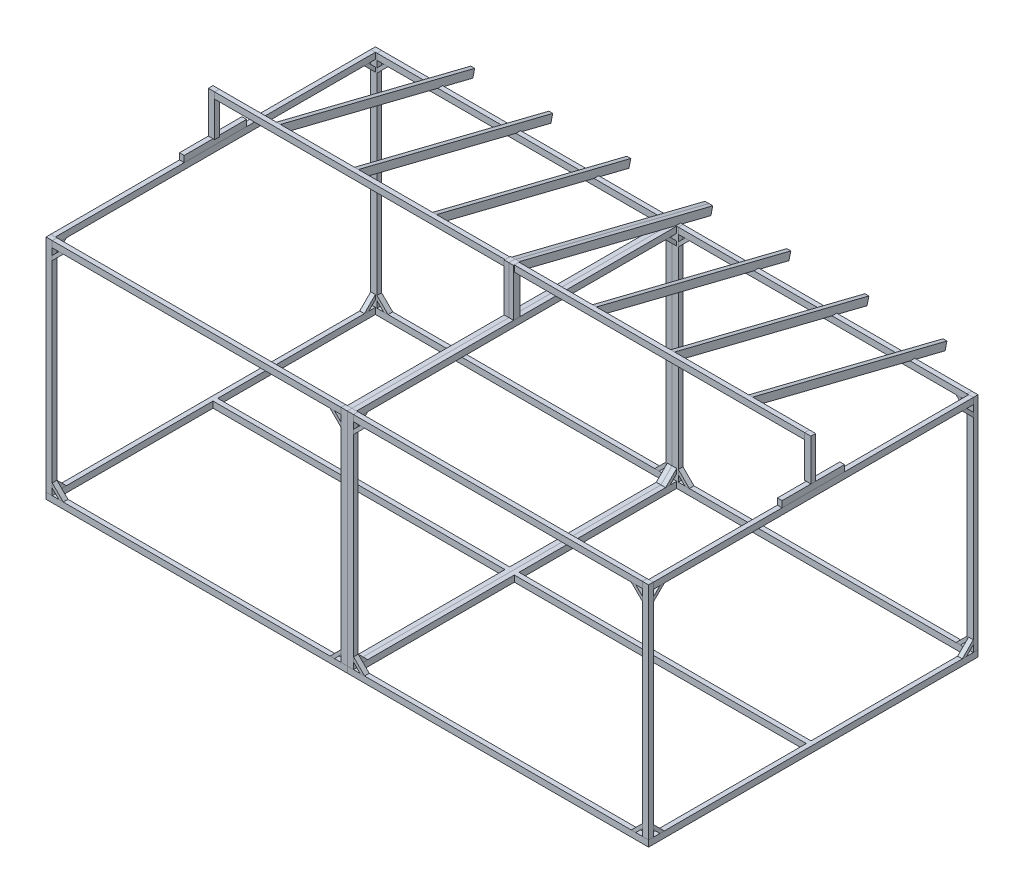
SolidWorks part; units mm, degrees
other "DetailItem8"
other "DetailItem9"
other "DetailItem10"
other "DetailItem12"
other "DetailItem13"
other "DetailItem14"
other "DetailItem15"
other "DetailItem16"
other "DetailItem17"
other "DetailItem18"
other "DetailItem19"
other "DetailItem21"
ref_plane "Front Plane" through (0, 0, 0) normal (0, 0, 1) x (1, 0, 0)
ref_plane "Top Plane" through (0, 0, 0) normal (0, 1, 0) x (1, 0, 0)
ref_plane "Right Plane" through (0, 0, 0) normal (1, 0, 0) x (0, 0, -1)
other "Configuration Table"
sketch "MetalBase" plane through (0, 0, 0) normal (0, 1, 0) x (1, 0, 0)
  line L0 (-60, -60) -> (7660, -60)
  line L1 (0, 0) -> (7600, 0)
  line L2 (0, 0) -> (0, 2020)
  line L3 (0, 4100) -> (7600, 4100)
  line L4 (7600, 0) -> (7600, 2020)
  line L5 (7660, -60) -> (7660, 4160)
  line L6 (-60, 4160) -> (7660, 4160)
  line L7 (-60, -60) -> (-60, 4160)
  line L8 (0, 2050) -> (7600, 2050) construction
  line L9 (0, 2020) -> (7600, 2020)
  line L10 (0, 2080) -> (7600, 2080)
  line L11 (0, 2080) -> (0, 4100)
  line L12 (7600, 2080) -> (7600, 4100)
  line L13 (0, 0) -> (0, 4100) construction
  line L15 (7600, 0) -> (7600, 4100) construction
  point P15 (7660, 2050)
  dimension "D1" = 4100
  dimension "D2" = 7600
  dimension "D6" = 4220
  dimension "D7" = 7720
  dimension "D3" = 60
  dimension "D4" = 30
  dimension "D5" = 30
sketch "InternalSpace" plane through (0, 0, 0) normal (0, 1, 0) x (1, 0, 0)
  line L26 (50, 50) -> (7550, 50)
  line L27 (7550, 50) -> (7550, 4050)
  line L28 (7550, 4050) -> (50, 4050)
  line L29 (50, 4050) -> (50, 50)
  line L30 (50, 50) -> (7550, 50)
  line L31 (7550, 50) -> (7550, 4050)
  line L32 (7550, 4050) -> (50, 4050)
  line L33 (50, 4050) -> (50, 50)
  dimension "D2" = 4000
  dimension "D3" = 7500
  dimension "D1" = 110
sketch "Furniture" [suppressed] plane through (0, 0, 0) normal (0, 1, 0) x (1, 0, 0)
  line L0 (6750, 2050) -> (6750, 4050)
  line L1 (2200, 2550) -> (1400, 2550)
  line L2 (2200, 2550) -> (2200, 4050)
  line L3 (2200, 4050) -> (1400, 4050)
  line L4 (1400, 2550) -> (1400, 4050)
  line L5 (1050, 50) -> (50, 50)
  line L6 (1050, 50) -> (1050, 2050)
  line L7 (1050, 2050) -> (50, 2050)
  line L8 (50, 50) -> (50, 2050)
  line L9 (6350, 2110) -> (7550, 2110)
  line L10 (2200, 4050) -> (2200, 150)
  line L11 (0, 0) -> (7600, 0) construction
  line L12 (6350, 50) -> (6350, 2110)
  line L13 (6470, 50) -> (6470, 1990)
  line L15 (2200, 2050) -> (7550, 2050) construction
  line L17 (1979.5569, 919.0285) -> (2200, 150)
  line L18 (6350, 150) -> (5722.0427, 459.305)
  line L19 (6710, 1120.0467) -> (7310, 1120.0467)
  line L24 (6710, 1120.0467) -> (6710, 1880.0467)
  line L25 (6710, 1880.0467) -> (7310, 1880.0467)
  line L26 (7310, 1120.0467) -> (7310, 1880.0467)
  line L27 (6350, 2110) -> (5750, 2110)
  line L28 (6350, 2110) -> (6350, 1510)
  line L29 (6350, 1510) -> (5750, 1510)
  line L30 (5750, 2110) -> (5750, 1510)
  line L31 (2320, 2050) -> (4320, 2050) construction
  line L32 (4320, 2050) -> (4320, 4050) construction
  line L33 (2200, 150) -> (2499.3532, 150) construction
  line L34 (2499.3532, 150) -> (2499.3532, 981.1813) construction
  line L35 (2499.3532, 981.1813) -> (2200, 981.1813) construction
  line L36 (2320, 4050) -> (2320, 150)
  line L37 (2200, 150) -> (2200, 50)
  line L38 (50, 50) -> (7550, 50) construction
  line L39 (2320, 150) -> (2320, 50)
  line L40 (7550, 4050) -> (50, 4050) construction
  line L41 (7550, 50) -> (7550, 4050) construction
  line L42 (50, 4050) -> (50, 50) construction
  line L43 (7550, 4050) -> (50, 4050) construction
  line L44 (7550, 50) -> (7550, 4050) construction
  line L45 (50, 50) -> (7550, 50) construction
  line L46 (50, 4050) -> (50, 50) construction
  line L47 (7010, 1120.0467) -> (7010, 1445.9123) construction
  line L48 (6470, 1990) -> (7550, 1990)
  line L49 (-60, -60) -> (-60, 4160) construction
  line L50 (7550, 809.8905) -> (7383.7397, 809.8905)
  line L51 (7550, 809.8905) -> (7550, 230.8186)
  line L52 (7550, 230.8186) -> (7383.7397, 230.8186)
  line L53 (7283.7397, 709.8905) -> (7283.7397, 330.8186)
  line L54 (7660, 4160) -> (-60, 4160) construction
  line L55 (-60, 4160) -> (-60, -60) construction
  line L56 (-60, -60) -> (7660, -60) construction
  line L57 (7660, -60) -> (7660, 4160) construction
  arc A1 (1979.5569, 919.0285) -> (1414.1883, 0) centre (2200, 150) ccw construction
  arc A2 (5722.0427, 459.305) -> (6350, 850) centre (6350, 150) cw construction
  arc A3 (7383.7397, 230.8186) -> (7283.7397, 330.8186) centre (7383.7397, 330.8186) cw
  arc A4 (7383.7397, 809.8905) -> (7283.7397, 709.8905) centre (7383.7397, 709.8905) ccw
  point P56 (7010, 1990)
  dimension "D13" = 600
  dimension "D21" = 100
  dimension "D1" = 1500
  dimension "D2" = 800
  dimension "D3" = 2000
  dimension "D4" = 1000
  dimension "D5" = 100
  dimension "D6" = 60
  dimension "D7" = 700
  dimension "D8" = 600
  dimension "D9" = 2260
  dimension "D10" = 800
  dimension "D11" = 100
  dimension "D12" = 760
  dimension "D14" = 2000
  dimension "D15" = 800
  dimension "D16" = 2000
  dimension "D17" = 600
  dimension "D18" = 60
  dimension "D19" = 4150
  dimension "D20" = 120
  dimension "D22" = 120
  dimension "D23" = 110
  dimension "D25" = 4220
  dimension "D26" = 1200
  dimension "D27" = 4030
  dimension "D24" = 110
sketch "Metal frame" plane through (0, 0, 0) normal (0, 1, 0) x (1, 0, 0)
  line L0 (0, 4100) -> (7600, 4100) construction
  line L1 (0, 4100) -> (7600, 4100)
  line L3 (0, 0) -> (0, 2020)
  line L4 (0, 0) -> (7600, 0) construction
  line L5 (0, 0) -> (7600, 0)
  line L7 (7600, 0) -> (7600, 2020)
  line L8 (-60, 4160) -> (7660, 4160)
  line L9 (7660, -60) -> (7660, 4160)
  line L10 (-60, -60) -> (7660, -60)
  line L11 (-60, -60) -> (-60, 4160)
  line L12 (0, 2050) -> (62.1159, 2050) construction
  line L13 (7600, 2080) -> (0, 2080)
  line L15 (7600, 2020) -> (0, 2020)
  line L17 (7600, 2080) -> (7600, 4100)
  line L18 (0, 2080) -> (0, 4100)
  line L19 (7600, 0) -> (7600, 4100) construction
  line L21 (0, 0) -> (0, 4100) construction
  point P14 (-60, 2050)
  dimension "D2" = 7720
  dimension "D3" = 4220
  dimension "D4" = 60
  dimension "D1" = 60
sketch "Walls bottom" plane through (0, 0, 0) normal (0, 1, 0) x (1, 0, 0)
  line L0 (-60, 4160) -> (7660, 4160) construction
  line L2 (-60, -60) -> (7660, -60) construction
  line L3 (7660, -60) -> (7660, 4160) construction
  line L4 (-60, -60) -> (-60, 4160) construction
  line L5 (-60, -60) -> (7660, -60)
  line L6 (7660, -60) -> (7660, 4160)
  line L7 (-60, 4160) -> (7660, 4160)
  line L8 (-60, -60) -> (-60, 4160)
  line L9 (40, 40) -> (40, 4060)
  line L10 (40, 4060) -> (7560, 4060)
  line L11 (7560, 40) -> (7560, 4060)
  line L12 (40, 40) -> (7560, 40)
  dimension "D2" = 4020
  dimension "D3" = 7520
  dimension "D4" = 7720
  dimension "D5" = 4220
  dimension "D1" = 100
sketch "Sketch15" [suppressed] plane through (0, 0, 0) normal (0, 1, 0) x (1, 0, 0)
  line L2 (7550, 50) -> (5502.4266, 50)
  line L3 (7550, 50) -> (7550, 1250)
  line L4 (7550, 1250) -> (5502.4266, 1250)
  line L5 (5502.4266, 50) -> (5502.4266, 1250)
  dimension "D1" = 1200
extrude "MetalFrame" add sketch "Metal frame" against normal blind 80 contours L11 L10 L9 L8 L15 L7 L5 L3 L13 L18 L1 L17 region at (3800, 0, -2050)
sketch "Sketch18" plane through (0, 0, 0) normal (0, 1, 0) x (1, 0, 0)
  line L0 (0, 0) -> (7600, 0) construction
  line L1 (3800, -1014.8769) -> (8467.9433, -1014.8769)
  line L2 (3800, -1014.8769) -> (3800, 5493.3133)
  line L3 (3800, 5493.3133) -> (8467.9433, 5493.3133)
  line L4 (8467.9433, -1014.8769) -> (8467.9433, 5493.3133)
  point P6 (3800, 0)
extrude "Cut-Extrude1" cut sketch "Sketch18" against normal through all
sketch "Sketch19" plane through (0, 0, 0) normal (0, 1, 0) x (1, 0, 0)
  line L0 (0, 0) -> (3800, 0) construction
  line L1 (3800, 4100) -> (3740, 4100)
  line L2 (3800, 4100) -> (3800, 0)
  line L3 (3800, 0) -> (3740, 0)
  line L4 (3740, 4100) -> (3740, 0)
  dimension "D1" = 60
extrude "Boss-Extrude1" add sketch "Sketch19" against normal blind 80
sketch "Roof" plane through (0, 0, 0) normal (1, 0, 0) x (0, 0, -1)
  line L0 (2050, 0) -> (2050, 3357.5) construction
  line L1 (4160, 0) -> (-60, 0) construction
  line L2 (4160, 0) -> (4160, 2830) construction
  line L3 (4160, 2830) -> (2050, 3357.5) construction
  line L4 (2050, 3357.5) -> (5424.8088, 3357.5) construction
  line L5 (4160, 2830) -> (4548.057, 2732.9857) construction
  line L6 (4160, 150) -> (-211.81, 150) construction
  line L7 (4160, 2830) -> (2960, 2830)
  line L8 (2960, 2830) -> (2960, 3130)
  line L9 (4160, 2750) -> (2401.0379, 2750) construction
  dimension "D2" = 1200
  dimension "D3" = 150
  dimension "D4" = 2174.9382
  dimension "D5" = 400
  dimension "D6" = 2574.9382
  dimension "D7" = 2830
  dimension "D8" = 300
  dimension "D9" = 3207.5
  dimension "D10" = 14.036
  dimension "D11" = 80
  dimension "D12" = 2600
sketch "Sketch23" plane through (-60, 0, 0) normal (1, 0, 0) x (0, 0, -1)
  line L0 (2050, 0) -> (2050, 3357.5) construction
  line L1 (4160, 0) -> (4100, 0)
  line L2 (4160, 0) -> (4160, 2830)
  line L3 (4160, 2830) -> (4100, 2830)
  line L4 (4100, 0) -> (4100, 2830)
  line L5 (0, 0) -> (0, 2830)
  line L6 (-60, 2830) -> (0, 2830)
  line L7 (-60, 0) -> (-60, 2830)
  line L8 (-60, 0) -> (0, 0)
  line L10 (0, 2830) -> (4100, 2830)
  line L11 (0, 2830) -> (0, 2750)
  line L12 (0, 2750) -> (4100, 2750)
  line L13 (4100, 2830) -> (4100, 2750)
  line M8 (-60, 0) -> (4160, 0)
  dimension "D1" = 60
  dimension "D2" = 80
extrude "Boss-Extrude5" add sketch "Sketch23" along normal blind 80 separate body contours L4 L3 L2 M8 | L7 L6 L5 M8 region at (-60, 1415, -4130) region at (-60, 1415, 30)
extrude "Boss-Extrude6" add sketch "Sketch23<3>" along normal blind 60 separate body contours L0 L12 L5 L10 | L12 L0 L10 L4 region at (-60, 2790, -1025) region at (-60, 2790, -3075)
sketch "Sketch23<3>" plane through (-60, 0, 0) normal (1, 0, 0) x (0, 0, -1) same geometry as "Sketch23"
extrude "Boss-Extrude7" add sketch "Sketch23<5>" against normal blind 80 from surface separate body contours L4 L3 L2 M8 | L7 L6 L5 M8 region at (-60, 1415, -4130) region at (-60, 1415, 30) starting at face at (3800, -40, -2050)
sketch "Sketch23<5>" plane through (-60, 0, 0) normal (1, 0, 0) x (0, 0, -1) same geometry as "Sketch23"
extrude "Boss-Extrude8" add sketch "Sketch23<6>" against normal blind 60 from surface separate body contours L12 L0 L10 L4 | L0 L12 L5 L10 region at (-60, 2790, -1025) region at (-60, 2790, -3075) starting at face at (3800, 1415, 30)
sketch "Sketch23<6>" plane through (-60, 0, 0) normal (1, 0, 0) x (0, 0, -1) same geometry as "Sketch23"
sketch "Sketch24" plane through (0, 2830, 0) normal (0, 1, 0) x (1, 0, 0)
  line L1 (20, 4160) -> (3720, 4160)
  line L2 (20, 4160) -> (20, 4100)
  line L3 (20, 4100) -> (3720, 4100)
  line L4 (3720, 4160) -> (3720, 4100)
  line L5 (20, 0) -> (3720, 0)
  line L6 (20, 0) -> (20, -60)
  line L7 (20, -60) -> (3720, -60)
  line L8 (3720, 0) -> (3720, -60)
extrude "Boss-Extrude9" add sketch "Sketch24" against normal blind 80 separate body
sketch "Sketch25" plane through (3800, 0, 0) normal (1, 0, 0) x (0, 0, -1)
  line L5 (2020, 2910) -> (2080, 2910)
  line L6 (2020, 2910) -> (2020, 3440)
  line L7 (2020, 3440) -> (2080, 3440)
  line L8 (2080, 2910) -> (2080, 3440)
  line L9 (2050, 0) -> (2050, 3357.5) construction
  line L10 (0, 2830) -> (4100, 2830) construction
  line L12 (1650, 2830) -> (2450, 2830)
  line L13 (1650, 2830) -> (1650, 2910)
  line L14 (1650, 2910) -> (2450, 2910)
  line L15 (2450, 2830) -> (2450, 2910)
  point P7 (2050, 3440)
  point P11 (2050, 2910)
  line M8 (4100, 2830) -> (0, 2830)
  dimension "D1" = 530
  dimension "D2" = 60
  dimension "D4" = 800
  dimension "D5" = 80
extrude "Boss-Extrude10" add sketch "Sketch25" along normal blind 80 from surface separate body contours L5 L8 L7 L6 region at (3800, 3175, -2050) starting at face at (-60, 2790, -2050)
extrude "Boss-Extrude13" add sketch "Sketch25<4>" against normal blind 60 from surface separate body contours L15 L14 L5 L13 M8 region at (3800, 2870, -2050) starting at face at (0, 2790, -2050)
sketch "Sketch25<4>" plane through (3800, 0, 0) normal (1, 0, 0) x (0, 0, -1) same geometry as "Sketch25"
extrude "Boss-Extrude20" add sketch "Sketch25<5>" against normal blind 60 separate body contours L15 L14 L5 L13 M8 region at (3800, 2870, -2050)
sketch "Sketch25<5>" plane through (3800, 0, 0) normal (1, 0, 0) x (0, 0, -1) same geometry as "Sketch25"
sketch "Sketch33" plane through (0, 2910, 0) normal (0, 1, 0) x (1, 0, 0)
  line L0 (3740, 1650) -> (3740, 2450) construction
  line L1 (3740, 2090) -> (3800, 2090)
  line L2 (3740, 2090) -> (3740, 2010)
  line L3 (3740, 2010) -> (3800, 2010)
  line L4 (3800, 2090) -> (3800, 2010)
  line L5 (3800, 1650) -> (3800, 2450) construction
  point P8 (3740, 2050)
  point P9 (3740, 2050)
  dimension "D1" = 80
extrude "Boss-Extrude21" add sketch "Sketch33" along normal up to surface (530 mm away) separate body up to face at (-20, 3440, -2050)
sketch "Sketch26" plane through (3800, 0, 0) normal (1, 0, 0) x (0, 0, -1)
  line L0 (4548.057, 2717.9857) -> (4160, 2815)
  line L1 (4548.057, 2717.9857) -> (4572.3106, 2815)
  line L3 (4572.3106, 2815) -> (2080, 3438.0776)
  line L4 (4100, 2815) -> (4100, 2830) construction
  line L5 (4100, 2830) -> (4160, 2830)
  line L6 (4160, 2830) -> (4160, 2815)
  line L7 (2080, 3335) -> (2080, 3438.0776)
  line L8 (4100, 2830) -> (2080, 3335)
  dimension "D1" = 100
extrude "Boss-Extrude12" add sketch "Sketch26" against normal blind 50 separate body
pattern_linear "LPattern1" count 4 spacing 1000 along (-1, 0, 0) of bodies 346
ref_plane "Plane1" through (1870, 0, 0) normal (-1, 0, 0) x (0, 0, 1)
sketch "Sketch27" plane through (3740, 0, 0) normal (-1, 0, 0) x (0, 0, 1)
  line L0 (-2020, 2910) -> (-2020, 3440) construction
  line L1 (-2080, 3440) -> (-2020, 3440)
  line L2 (-2080, 3440) -> (-2080, 3360)
  line L3 (-2080, 3360) -> (-2020, 3360)
  line L4 (-2020, 3440) -> (-2020, 3360)
  line L5 (-2050, 0) -> (-2050, 3357.5) construction
  point P4 (-2050, 3440)
  dimension "D1" = 80
  dimension "D2" = 60
extrude "Boss-Extrude22" add sketch "Sketch27" along normal up to surface (3720 mm away) separate body up to face at (20, 3175, -2050)
mirror "Mirror2" about plane through (3800, -80, 1014.8769) normal (-1, 0, 0) of bodies 336 338 340 342 335 337 339 341 330 412 411 349 348 347 346 410 350 351 354 352 353
sketch "Sketch28" plane through (0, 0, 60) normal (0, 0, 1) x (1, 0, 0)
  line L0 (20, 2665.1472) -> (104.8528, 2750)
  line L1 (20, 2750) -> (3720, 2750) construction
  line L2 (20, 0) -> (20, 2830) construction
  line L3 (20, 2608.5786) -> (161.4214, 2750)
  line L4 (20, 2665.1472) -> (20, 2750) construction
  line L5 (20, 2750) -> (104.8528, 2750) construction
  line L6 (3720, 2750) -> (20, 0) construction
  line L7 (20, 2750) -> (3720, 0) construction
  line L8 (104.8528, 2750) -> (161.4214, 2750)
  line L9 (20, 2665.1472) -> (20, 2608.5786)
  line L10 (1870, 1375) -> (1870, 2476.0047) construction
  line L11 (1870, 1375) -> (689.8346, 1375) construction
  line L12 (20, 0) -> (104.8528, 0) construction
  line L13 (20, 84.8528) -> (20, 0) construction
  line L14 (20, 84.8528) -> (20, 141.4214)
  line L15 (104.8528, 0) -> (161.4214, 0)
  line L16 (20, 141.4214) -> (161.4214, 0)
  line L17 (20, 84.8528) -> (104.8528, 0)
  line L18 (3720, 84.8528) -> (3720, 0) construction
  line L19 (3720, 0) -> (3635.1472, 0) construction
  line L20 (3720, 2750) -> (3635.1472, 2750) construction
  line L21 (3720, 2665.1472) -> (3720, 2750) construction
  line L22 (3720, 84.8528) -> (3635.1472, 0)
  line L23 (3720, 141.4214) -> (3578.5786, 0)
  line L24 (3635.1472, 0) -> (3578.5786, 0)
  line L25 (3720, 84.8528) -> (3720, 141.4214)
  line L26 (3720, 2665.1472) -> (3720, 2608.5786)
  line L27 (3635.1472, 2750) -> (3578.5786, 2750)
  line L28 (3720, 2608.5786) -> (3578.5786, 2750)
  line L29 (3720, 2665.1472) -> (3635.1472, 2750)
  line L30 (3800, -80) -> (3800, -237.922) construction
  line L31 (3880, 2665.1472) -> (3880, 2750) construction
  line L32 (3880, 2750) -> (3964.8528, 2750) construction
  line L33 (3880, 0) -> (3964.8528, 0) construction
  line L34 (3880, 84.8528) -> (3880, 0) construction
  line L35 (7580, 84.8528) -> (7580, 0) construction
  line L36 (7580, 0) -> (7495.1472, 0) construction
  line L37 (5730, 1375) -> (6910.1654, 1375) construction
  line L38 (5730, 1375) -> (5730, 2476.0047) construction
  line L39 (7580, 2750) -> (3880, 0) construction
  line L40 (3880, 2750) -> (7580, 0) construction
  line L41 (7580, 2750) -> (7495.1472, 2750) construction
  line L42 (7580, 2665.1472) -> (7580, 2750) construction
  line L43 (3880, 2665.1472) -> (3964.8528, 2750)
  line L44 (3880, 2608.5786) -> (4021.4214, 2750)
  line L45 (3964.8528, 2750) -> (4021.4214, 2750)
  line L46 (3880, 2665.1472) -> (3880, 2608.5786)
  line L47 (3880, 84.8528) -> (3880, 141.4214)
  line L48 (3964.8528, 0) -> (4021.4214, 0)
  line L49 (3880, 141.4214) -> (4021.4214, 0)
  line L50 (3880, 84.8528) -> (3964.8528, 0)
  line L51 (7580, 84.8528) -> (7495.1472, 0)
  line L52 (7580, 141.4214) -> (7438.5786, 0)
  line L53 (7495.1472, 0) -> (7438.5786, 0)
  line L54 (7580, 84.8528) -> (7580, 141.4214)
  line L55 (7580, 2665.1472) -> (7580, 2608.5786)
  line L56 (7495.1472, 2750) -> (7438.5786, 2750)
  line L57 (7580, 2608.5786) -> (7438.5786, 2750)
  line L58 (7580, 2665.1472) -> (7495.1472, 2750)
  point P14 (1870, 1375)
  point P58 (5730, 1375)
  dimension "D1" = 40
  dimension "D2" = 200
extrude "Boss-Extrude15" add sketch "Sketch28" against normal blind 60 separate body
ref_plane "Plane2" through (0, 0, -2050) normal (0, 0, 1) x (1, 0, 0)
mirror "Mirror5" about plane through (0, 0, -2050) normal (0, 0, 1) of bodies 379 382 378 377 380 381 384 383
sketch "Sketch29" plane through (-60, 0, 0) normal (-1, 0, 0) x (0, 0, 1)
  line L0 (-141.4214, 2750) -> (0, 2608.5786)
  line L1 (0, 2750) -> (-4100, 2750) construction
  line L2 (0, 0) -> (0, 2830) construction
  line L3 (0, 2608.5786) -> (0, 2665.1472)
  line L4 (0, 2665.1472) -> (-84.8528, 2750)
  line L5 (-84.8528, 2750) -> (-141.4214, 2750)
  line L6 (-141.4214, 2750) -> (0, 2750) construction
  line L7 (0, 2750) -> (0, 2608.5786) construction
  line L8 (-4100, 2750) -> (0, 0) construction
  line L9 (0, 2750) -> (-4100, 0) construction
  line L10 (-2050, 1375) -> (-2050, 2472.0101) construction
  line L11 (-2050, 0) -> (-2050, 3357.5) construction
  line L12 (-2050, 1375) -> (-3378.9698, 1375) construction
  line L13 (-4100, 2750) -> (-4100, 2608.5786) construction
  line L14 (-3958.5786, 2750) -> (-4100, 2750) construction
  line L15 (-4015.1472, 2750) -> (-3958.5786, 2750)
  line L16 (-4100, 2665.1472) -> (-4015.1472, 2750)
  line L17 (-4100, 2608.5786) -> (-4100, 2665.1472)
  line L18 (-3958.5786, 2750) -> (-4100, 2608.5786)
  line L19 (-3958.5786, 0) -> (-4100, 0) construction
  line L20 (-4100, 0) -> (-4100, 141.4214) construction
  line L21 (0, 0) -> (0, 141.4214) construction
  line L22 (-141.4214, 0) -> (0, 0) construction
  line L23 (-3958.5786, 0) -> (-4100, 141.4214)
  line L24 (-4100, 141.4214) -> (-4100, 84.8528)
  line L25 (-4100, 84.8528) -> (-4015.1472, 0)
  line L26 (-4015.1472, 0) -> (-3958.5786, 0)
  line L27 (-84.8528, 0) -> (-141.4214, 0)
  line L28 (0, 84.8528) -> (-84.8528, 0)
  line L29 (0, 141.4214) -> (0, 84.8528)
  line L30 (-141.4214, 0) -> (0, 141.4214)
  dimension "D1" = 200
  dimension "D2" = 40
extrude "Boss-Extrude16" add sketch "Sketch29" against normal blind 60 separate body
extrude "Boss-Extrude17" add sketch "Sketch29<2>" against normal blind 60 from surface separate body starting at face at (3740, 2790, -2050)
sketch "Sketch29<2>" plane through (-60, 0, 0) normal (-1, 0, 0) x (0, 0, 1) same geometry as "Sketch29"
extrude "Boss-Extrude18" add sketch "Sketch29<4>" against normal blind 60 from surface separate body starting at face at (3800, 2790, -2050)
sketch "Sketch29<4>" plane through (-60, 0, 0) normal (-1, 0, 0) x (0, 0, 1) same geometry as "Sketch29"
extrude "Boss-Extrude19" add sketch "Sketch29<5>" against normal blind 60 from surface separate body starting at face at (7600, 2790, -2050)
sketch "Sketch29<5>" plane through (-60, 0, 0) normal (-1, 0, 0) x (0, 0, 1) same geometry as "Sketch29"
delete or keep bodies "Body-Delete/Keep 1" type delete bodies bodies 410 415
sketch "Sketch34" plane through (0, 2910, 0) normal (0, -1, 0) x (1, 0, 0)
  line L4 (3740, -2010) -> (3740, -2090)
  line L5 (3740, -2090) -> (3800, -2090)
  line L6 (3800, -2090) -> (3800, -2010)
  line L7 (3800, -2010) -> (3740, -2010)
  line L8 (3740, -2010) -> (3740, -2090)
  line L9 (3740, -2090) -> (3800, -2090)
  line L10 (3800, -2090) -> (3800, -2010)
  line L11 (3800, -2010) -> (3740, -2010)
  dimension "D1" = 0
extrude "Boss-Extrude23" add sketch "Sketch34" along normal up to surface (80 mm away) up to face at (3830, 2830, -2050)
sketch "Sketch35" plane through (0, 2910, 0) normal (0, -1, 0) x (1, 0, 0)
  line L4 (3860, -2090) -> (3860, -2010)
  line L5 (3860, -2010) -> (3800, -2010)
  line L6 (3800, -2010) -> (3800, -2090)
  line L7 (3800, -2090) -> (3860, -2090)
  line L8 (3860, -2090) -> (3860, -2010)
  line L9 (3860, -2010) -> (3800, -2010)
  line L10 (3800, -2010) -> (3800, -2090)
  line L11 (3800, -2090) -> (3860, -2090)
  dimension "D1" = 0
extrude "Boss-Extrude24" add sketch "Sketch35" along direction (0, -1, 0) on the side of the normal up to surface (80 mm away) up to face at (3830, 2830, -2050)
